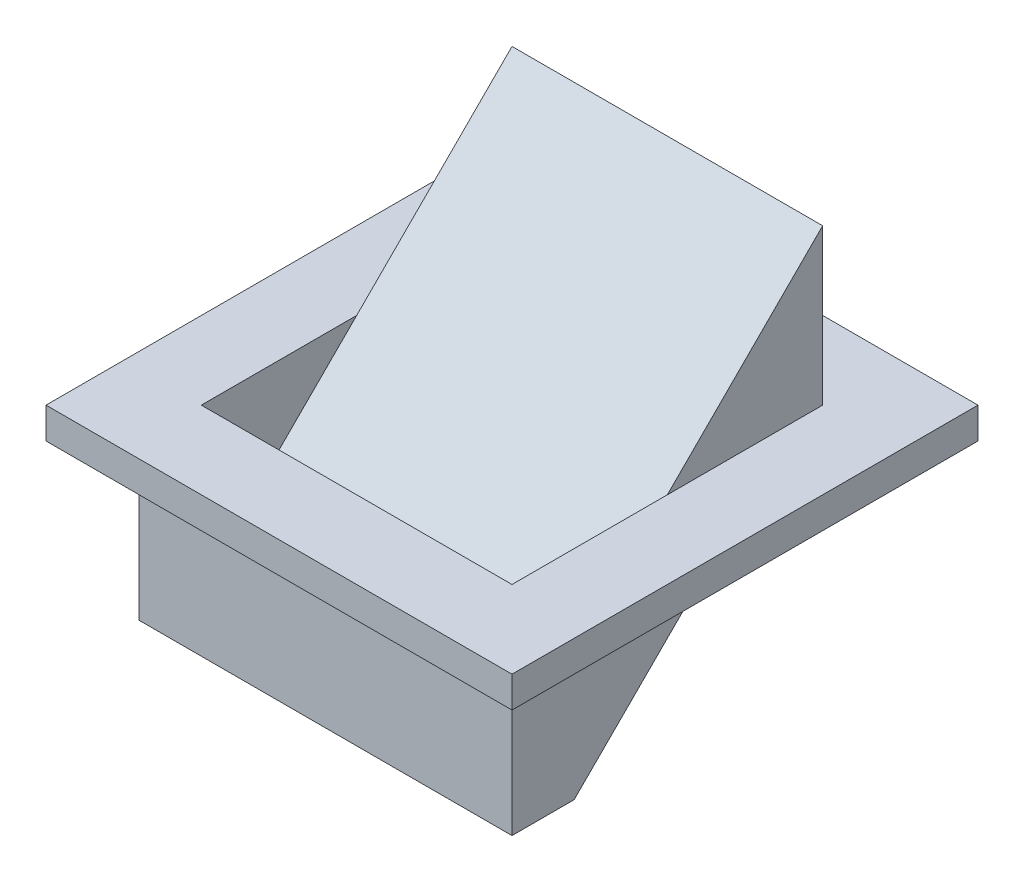
SolidWorks part; units mm, degrees
ref_plane "Front Plane" through (0, 0, 0) normal (0, 0, 1) x (1, 0, 0)
ref_plane "Top Plane" through (0, 0, 0) normal (0, 1, 0) x (1, 0, 0)
ref_plane "Right Plane" through (0, 0, 0) normal (1, 0, 0) x (0, 0, -1)
sketch "Sketch1" plane through (0, 0, 0) normal (0, 1, 0) x (1, 0, 0)
  line L1 (0, 0) -> (150, 0)
  line L2 (0, 0) -> (0, 150)
  line L3 (0, 150) -> (150, 150)
  line L4 (150, 0) -> (150, 150)
  dimension "D1" = 150
  dimension "D2" = 150
extrude "Boss-Extrude1" add sketch "Sketch1" along normal blind 10
sketch "Sketch3" plane through (0, 10, 0) normal (0, 1, 0) x (1, 0, 0)
  line L0 (150, 150) -> (0, 150) construction
  line L1 (25, 25) -> (125, 25)
  line L2 (25, 25) -> (25, 125)
  line L3 (25, 125) -> (125, 125)
  line L4 (125, 25) -> (125, 125)
  line L5 (0, -5.5) -> (0, 5.5) construction
  line L6 (25, 75) -> (125, 75)
  dimension "D1" = 100
  dimension "D2" = 100
  dimension "D3" = 25
  dimension "D4" = 25
extrude "Boss-Extrude2" add sketch "Sketch3" along normal blind 50 contours L2 L6 L4 L3 region at (75, 10, -100)
sketch "Sketch4" plane through (25, 0, 0) normal (-1, 0, 0) x (0, 0, 1)
  line L0 (-125, 60) -> (-75, 10)
  line L1 (-75, 60) -> (-125, 60) construction
  line L2 (-125, 60) -> (-125, 10) construction
  line L3 (-75, 10) -> (-125, 10) construction
  line L4 (-75, 10) -> (-75, 60)
  line L5 (-75, 60) -> (-125, 60)
extrude "Cut-Extrude1" cut sketch "Sketch4" against normal through all
sketch "Sketch5" plane through (0, 10, 0) normal (0, 1, 0) x (1, 0, 0)
  line L0 (25, 75) -> (25, 25)
  line L1 (25, 25) -> (125, 25)
  line L2 (125, 25) -> (125, 75)
  line L3 (125, 75) -> (25, 75)
  dimension "D1" = 100
  dimension "D2" = 50
extrude "Cut-Extrude2" cut sketch "Sketch5" against normal through all
sketch "Sketch6" plane through (25, 0, 0) normal (1, 0, 0) x (0, 0, -1)
  line L0 (75, 10) -> (25, 10)
  line L1 (25, 10) -> (25, -40)
  line L2 (25, -40) -> (75, 10)
  line L3 (25, 0) -> (65, 0)
  line L4 (75, 0) -> (25, 0) construction
  line L5 (65, 0) -> (75, 0)
  line L6 (75, 0) -> (75, 10)
  line M3 (25, 0) -> (75, 0)
  line M4 (75, 0) -> (75, 10)
  dimension "D1" = 50
sketch "Sketch7" plane through (0, 0, 0) normal (0, -1, 0) x (1, 0, 0)
  line L0 (125, -75) -> (25, -75) construction
  line L1 (135, -85) -> (15, -85)
  line L2 (135, -85) -> (135, -15)
  line L3 (135, -15) -> (15, -15)
  line L4 (15, -85) -> (15, -15)
  line L6 (25, -25) -> (125, -25) construction
  line L7 (125, -25) -> (125, -75) construction
  line L8 (25, -75) -> (25, -25) construction
  dimension "D1" = 10
  dimension "D2" = 10
  dimension "D3" = 10
  dimension "D4" = 10
extrude "Boss-Extrude6" add sketch "Sketch7" along normal blind 50
extrude "Boss-Extrude7" add sketch "Sketch6" along normal blind 100 contours L2 M3 M4 region at (25, 3.3333, -71.6667)
sketch "Sketch9" plane through (0, 0, 0) normal (0, 1, 0) x (1, 0, 0)
  line L1 (25, 65) -> (125, 65)
  line L2 (25, 65) -> (25, 25)
  line L3 (25, 25) -> (125, 25)
  line L4 (125, 65) -> (125, 25)
extrude "Cut-Extrude4" cut sketch "Sketch9" against normal blind 40
sketch "Sketch10" plane through (25, 0, 0) normal (1, 0, 0) x (0, 0, -1)
  line L0 (65, 0) -> (25, -40)
  line L1 (25, -40) -> (65, -40)
  line L2 (65, -40) -> (65, 0)
extrude "Boss-Extrude8" add sketch "Sketch10" along normal blind 100
sketch "Sketch11" plane through (135, 0, 0) normal (1, 0, 0) x (0, 0, -1)
  line L0 (85, 0) -> (85, -50)
  line L1 (85, -50) -> (35, -50)
  line L2 (85, -50) -> (15, -50) construction
  line L3 (35, -50) -> (85, 0)
  dimension "D1" = 50
extrude "Cut-Extrude5" cut sketch "Sketch11" against normal through all
shell "Shell1" thickness 10 removed face at (75, 35, -125)
